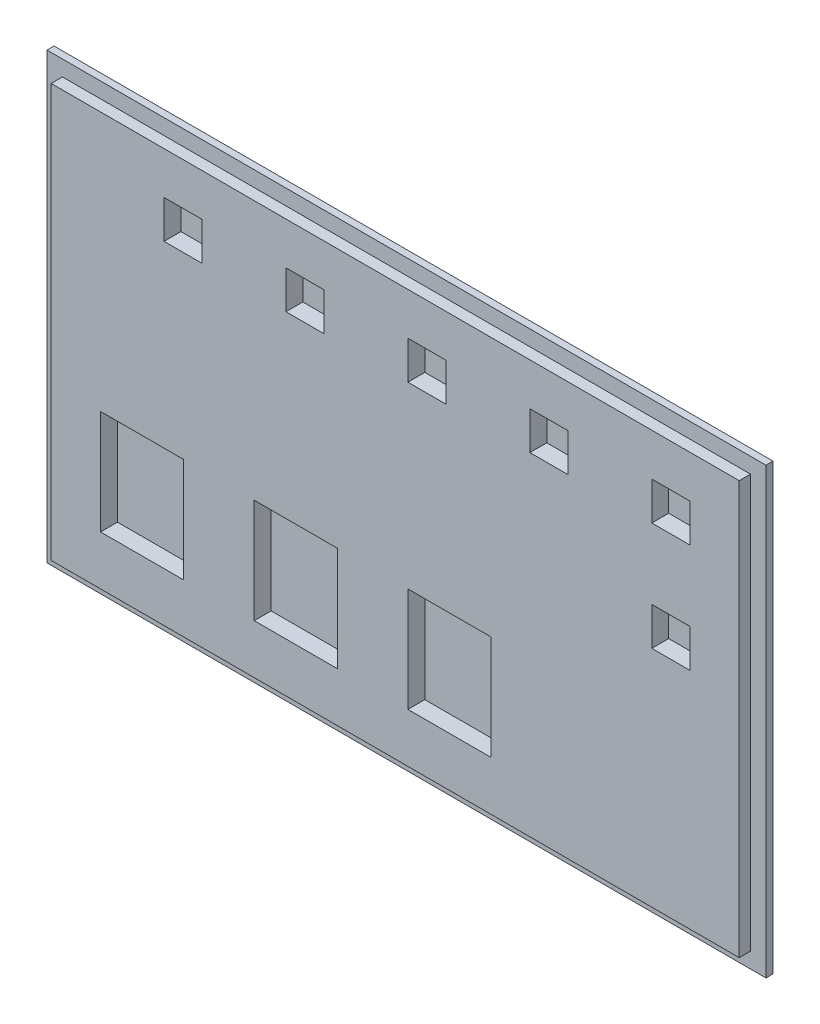
SolidWorks part; units mm, degrees
ref_plane "Přední rovina" through (0, 0, 0) normal (0, 0, 1) x (1, 0, 0)
ref_plane "Horní rovina" through (0, 0, 0) normal (0, 1, 0) x (1, 0, 0)
ref_plane "Pravá rovina" through (0, 0, 0) normal (1, 0, 0) x (0, 0, -1)
sketch "Skica1" plane through (0, 0, 0) normal (0, 0, 1) x (1, 0, 0)
  line L1 (0, 0) -> (102, 0)
  line L2 (0, 0) -> (0, 63)
  line L3 (0, 63) -> (102, 63)
  line L4 (102, 0) -> (102, 63)
  line L25 (18.2, 54.8) -> (23.6, 54.8)
  line L26 (18.2, 54.8) -> (18.2, 49.4)
  line L27 (18.2, 49.4) -> (23.6, 49.4)
  line L28 (23.6, 54.8) -> (23.6, 49.4)
  line L29 (35.5, 54.8) -> (40.9, 54.8)
  line L30 (35.5, 54.8) -> (35.5, 49.4)
  line L31 (35.5, 49.4) -> (40.9, 49.4)
  line L32 (40.9, 54.8) -> (40.9, 49.4)
  line L33 (52.8, 54.8) -> (58.2, 54.8)
  line L34 (52.8, 54.8) -> (52.8, 49.4)
  line L35 (52.8, 49.4) -> (58.2, 49.4)
  line L36 (58.2, 54.8) -> (58.2, 49.4)
  line L37 (70.1, 54.8) -> (75.5, 54.8)
  line L38 (70.1, 54.8) -> (70.1, 49.4)
  line L39 (70.1, 49.4) -> (75.5, 49.4)
  line L40 (75.5, 54.8) -> (75.5, 49.4)
  line L41 (87.4, 54.8) -> (92.8, 54.8)
  line L42 (87.4, 54.8) -> (87.4, 49.4)
  line L43 (87.4, 49.4) -> (92.8, 49.4)
  line L44 (92.8, 54.8) -> (92.8, 49.4)
  line L45 (2.2, 60.8) -> (99.8, 60.8)
  line L46 (2.2, 60.8) -> (2.2, 2.2)
  line L47 (2.2, 2.2) -> (99.8, 2.2)
  line L48 (99.8, 60.8) -> (99.8, 2.2)
  line L49 (9.2, 24) -> (21, 24)
  line L50 (9.2, 24) -> (9.2, 9.2)
  line L51 (9.2, 9.2) -> (21, 9.2)
  line L52 (21, 24) -> (21, 9.2)
  line L53 (31, 24) -> (42.8, 24)
  line L54 (31, 24) -> (31, 9.2)
  line L55 (31, 9.2) -> (42.8, 9.2)
  line L56 (42.8, 24) -> (42.8, 9.2)
  line L57 (52.8, 24) -> (64.6, 24)
  line L58 (52.8, 24) -> (52.8, 9.2)
  line L59 (52.8, 9.2) -> (64.6, 9.2)
  line L60 (64.6, 24) -> (64.6, 9.2)
  line L63 (87.4, 39.4) -> (92.8, 39.4)
  line L65 (87.4, 39.4) -> (87.4, 34)
  line L66 (87.4, 34) -> (92.8, 34)
  line L67 (92.8, 39.4) -> (92.8, 34)
  point P29 (90.1, 54.8)
  dimension "D2" = 5.4
  dimension "D3" = 5.4
  dimension "D4" = 7
  dimension "D5" = 6
  dimension "D6" = 5.4
  dimension "D7" = 5.4
  dimension "D8" = 5.4
  dimension "D9" = 5.4
  dimension "D10" = 5.4
  dimension "D11" = 5.4
  dimension "D12" = 5.4
  dimension "D13" = 5.4
  dimension "D14" = 11.9
  dimension "D15" = 102
  dimension "D16" = 11.9
  dimension "D17" = 11.9
  dimension "D18" = 63
  dimension "D19" = 11.9
  dimension "D20" = 2.2
  dimension "D21" = 2.2
  dimension "D22" = 2.2
  dimension "D23" = 2.2
  dimension "D24" = 6
  dimension "D25" = 11.8
  dimension "D26" = 14.8
  dimension "D27" = 11.8
  dimension "D28" = 11.8
  dimension "D32" = 7
  dimension "D33" = 7
  dimension "D34" = 10
  dimension "D35" = 10
  dimension "D36" = 5.4
  dimension "D37" = 5.4
  dimension "D38" = 10
  dimension "D39" = 97.6
extrude "Přidat vysunutím1" add sketch "Skica1" along normal blind 2.6 contours L48 L45 L46 L47 L25 L28 L27 L26 L29 L32 L31 L30 L33 L36 L35 L34 L37 L40 L39 L38 L41 L44 L43 L42 L49 L52 L51 L50 L53 L56 L55 L54 L57 L60 L59 L58 region at (52.1136, 32.4265, 0)
extrude "Přidat vysunutím2" add sketch "Skica1<3>" along normal blind 1 contours L1 L4 L3 L2 L45 L48 L47 L46 region at (1.1989, 31.5, 0)
sketch "Skica1<3>" plane through (0, 0, 0) normal (0, 0, 1) x (1, 0, 0) same geometry as "Skica1"
extrude "Přidat vysunutím3" add sketch "Skica1<5>" along normal blind 0.2 contours L58 L59 L60 | L54 L55 L56 | L52 L50 L51 | L67 L63 L65 L66 | L44 L41 L42 L43 | L40 L37 L38 L39 | L36 L33 L34 L35 | L32 L29 L30 L31 | L28 L25 L26 L27 region at (20.9, 52.1, 0) region at (38.2, 52.1, 0) region at (55.5, 52.1, 0) region at (72.8, 52.1, 0) region at (90.1, 52.1, 0) region at (15.1, 16.6, 0) region at (36.9, 16.6, 0) region at (58.7, 16.6, 0) region at (90.1, 36.7, 0)
sketch "Skica1<5>" plane through (0, 0, 0) normal (0, 0, 1) x (1, 0, 0) same geometry as "Skica1"
